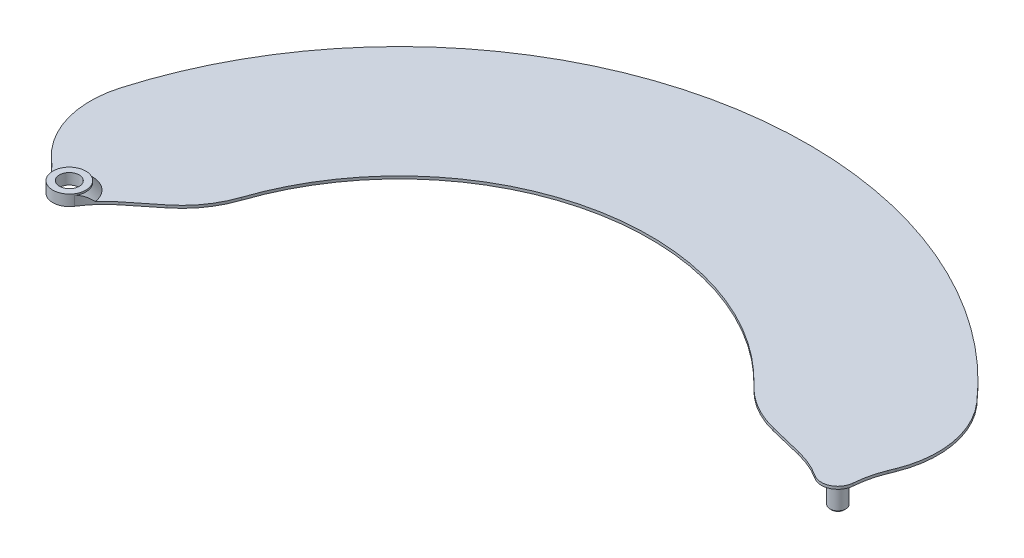
SolidWorks part; units mm, degrees
ref_plane "Front Plane" through (0, 0, 0) normal (0, 0, 1) x (1, 0, 0)
ref_plane "Top Plane" through (0, 0, 0) normal (0, 1, 0) x (1, 0, 0)
ref_plane "Right Plane" through (0, 0, 0) normal (1, 0, 0) x (0, 0, -1)
sketch "Sketch1" plane through (0, 0, 0) normal (0, 1, 0) x (1, 0, 0)
  line L0 (0, 0) -> (-50, 0) construction
  arc A0 (-50, 0) -> (45.3154, 21.1309) centre (0, 0) cw construction
  arc A1 (56.1911, 26.2023) -> (-62, 0) centre (0, 0) ccw
  arc A2 (34.4397, 16.0595) -> (-38, 0) centre (0, 0) ccw
  arc A3 (34.4397, 16.0595) -> (56.1911, 26.2023) centre (45.3154, 21.1309) ccw
  arc A4 (-62, 0) -> (-38, 0) centre (-50, 0) ccw
  point P3 (-10.822, 48.8148)
  dimension "D2" = 12
  dimension "D3" = 50
  dimension "D1" = 155
extrude "Boss-Extrude1" add sketch "Sketch1" along normal mid plane 0.4
sketch "Sketch2" plane through (0, 0.2, 0) normal (0, 1, 0) x (1, 0, 0)
  arc A0 (-62, 0) -> (-38, 0) centre (-50, 0) ccw construction
  arc A1 (-62, 0) -> (-38, 0) centre (-50, 0) ccw
  circle A2 centre (-50, 0) radius 1
  dimension "D1" = 2
extrude "Boss-Extrude2" add sketch "Sketch2" along normal blind 4 contours A2 region at (-50, 0.2, 0)
sketch "Sketch3" plane through (0, -0.2, 0) normal (0, -1, 0) x (1, 0, 0)
  arc A0 (56.1911, -26.2023) -> (34.4397, -16.0595) centre (45.3154, -21.1309) ccw construction
  arc A1 (56.1911, -26.2023) -> (34.4397, -16.0595) centre (45.3154, -21.1309) ccw
  circle A2 centre (45.3154, -21.1309) radius 1.2
  dimension "D1" = 2.4
extrude "Boss-Extrude3" add sketch "Sketch3" along normal blind 4 contours A2 region at (45.3154, -0.2, -21.1309)
sketch "Sketch4" plane through (0, 0.2, 0) normal (0, 1, 0) x (1, 0, 0)
  line L0 (0, 0) -> (-13.4193, 60.5304) construction
  line L1 (-47.5, 0) -> (-37.075, 8.3333)
  line L2 (-52.5, 0) -> (-61.4374, 8.3333)
  line L3 (43.0496, 20.0744) -> (30.0795, 23.2211)
  line L4 (47.5812, 22.1875) -> (52.1594, 33.5171)
  arc A0 (-52.5, 0) -> (-47.5, 0) centre (-50, 0) ccw
  arc A1 (47.5812, 22.1875) -> (43.0496, 20.0744) centre (45.3154, 21.1309) cw
  arc A5 (34.4397, 16.0595) -> (56.1911, 26.2023) centre (45.3154, 21.1309) ccw
  arc A6 (56.1911, 26.2023) -> (-62, 0) centre (0, 0) ccw
  arc A7 (-62, 0) -> (-38, 0) centre (-50, 0) ccw
  arc A8 (34.4397, 16.0595) -> (-38, 0) centre (0, 0) ccw
  arc A9 (34.4397, 16.0595) -> (56.1911, 26.2023) centre (45.3154, 21.1309) ccw
  arc A10 (56.1911, 26.2023) -> (-62, 0) centre (0, 0) ccw
  arc A11 (-62, 0) -> (-38, 0) centre (-50, 0) ccw
  arc A12 (34.4397, 16.0595) -> (-38, 0) centre (0, 0) ccw
  arc M6 (34.4397, 16.0595) -> (56.1911, 26.2023) centre (45.3154, 21.1309) ccw
  arc M7 (56.1911, 26.2023) -> (-62, 0) centre (0, 0) ccw
  arc M8 (-62, 0) -> (-38, 0) centre (-50, 0) ccw
  dimension "D2" = 5
  dimension "D3" = 8.3333
  dimension "D4" = 8.3333
extrude "Cut-Extrude1" cut sketch "Sketch4" against normal through all both and the other way through all contours M8 M7 | M6 M7 | M8 | M6 region at (-50.0192, 0.2, 3.1313) region at (46.6561, 0.2, -18.3011)
fillet "Fillet1" radius 14.2857 8 edges at (-37.075, 0, -8.3333) (-61.4374, 0, -8.3333) (-52.5, 0, 0) (-47.5, 0, 0) (52.1594, 0, -33.5171) (47.5812, 0, -22.1875) (43.0496, 0, -20.0744) (30.0795, 0, -23.2211)
sketch "Sketch5" plane through (0, 0.2, 0) normal (0, 1, 0) x (1, 0, 0)
  circle A0 centre (-50, 0) radius 2.5
  circle A1 centre (-50, 0) radius 1 construction
  dimension "D1" = 5
extrude "Boss-Extrude4" add sketch "Sketch5" along normal blind 1.25
chamfer "Chamfer1" distance 1 angle 45 1 edges at (-49.9387, 0.2, -2.4992)
sketch "Sketch6" plane through (0, 4.2, 0) normal (0, 1, 0) x (1, 0, 0)
  circle A2 centre (-50, 0) radius 1.5
  dimension "D1" = 3
extrude "Cut-Extrude2" cut sketch "Sketch6" against normal up to next
fillet "Fillet2" radius 0.75 1 edges at (45.3154, -0.2, -19.9309)
chamfer "Chamfer2" distance 0.25 angle 45 1 edges at (45.3154, -4.2, -22.3309)
equation "\"D1@Sketch1\" = \"Arc Angle\""
equation "\"D2@Sketch1\"=\"Arc Thickness\""
equation "\"D3@Sketch1\" = \"Arc Radius\""
equation "\"Arcs\" = 10"
equation "\"Pivital Radius\"= 100"
equation "\"Ring Thickness\"= 40"
equation "\"Arc Angle\"= 155deg"
equation "\"Arc Thickness\"= 12"
equation "\"Arc Radius\"= 50"
equation "\"D3@Sketch4\"=\"Arc Radius\"/6"
equation "\"D4@Sketch4\"=\"D3@Sketch4\""
equation "\"D1@Fillet1\"=\"Arc Radius\"/3.5"
